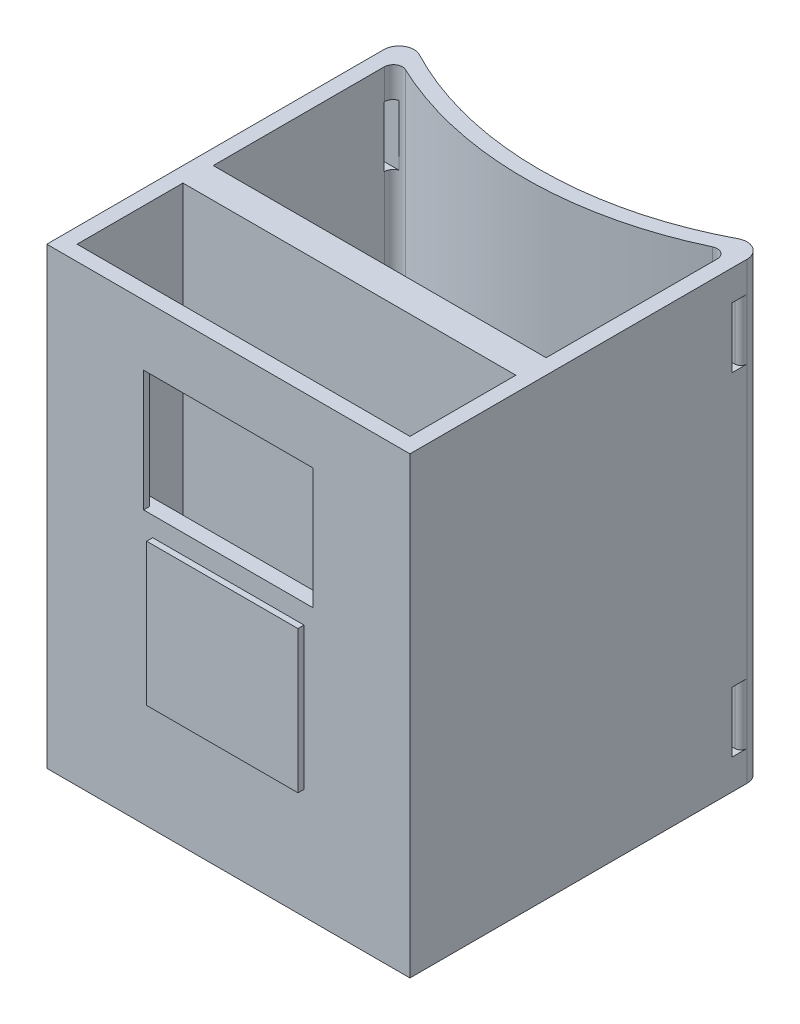
SolidWorks part; units mm, degrees
ref_plane "Front Plane" through (0, 0, 0) normal (0, 0, 1) x (1, 0, 0)
ref_plane "Top Plane" through (0, 0, 0) normal (0, 1, 0) x (1, 0, 0)
ref_plane "Right Plane" through (0, 0, 0) normal (1, 0, 0) x (0, 0, -1)
sketch "Sketch1" plane through (0, 0, 0) normal (0, 1, 0) x (1, 0, 0)
  line L1 (-60, -60) -> (60, -60)
  line L2 (-60, -60) -> (-60, 60)
  line L3 (-60, 60) -> (60, 60)
  line L4 (60, -60) -> (60, 60)
  line L5 (-60, -60) -> (60, 60) construction
  line L6 (-60, 60) -> (60, -60) construction
  point P0 (0, 0)
  dimension "D1" = 120
  dimension "D2" = 120
extrude "Boss-Extrude1" add sketch "Sketch1" along normal blind 150
sketch "Sketch2" plane through (0, 150, 0) normal (0, 1, 0) x (1, 0, 0)
  arc A0 (-60, 60) -> (60, 60) centre (0, 155.9682) ccw
extrude "Cut-Extrude1" cut sketch "Sketch2" against normal blind 150 and the other way through all
shell "Shell1" thickness 5 removed face at (0, 150, 4.3032)
sketch "Sketch3" plane through (0, 0, 0) normal (0, -1, 0) x (1, 0, 0)
  line L0 (60, 60) -> (60, -60) construction
  line L4 (-60, 60) -> (60, 60) construction
  circle A0 centre (0, 35) radius 2.5
  circle A1 centre (-5, 25) radius 1.5
  circle A2 centre (5, 25) radius 1.5
  point P9 (0, 0)
  dimension "D3" = 5
  dimension "D4" = 3
  dimension "D5" = 10
  dimension "D6" = 55
  dimension "D7" = 10
  dimension "D8" = 35
  dimension "D1" = 35
  dimension "D2" = 60
extrude "Cut-Extrude2" cut sketch "Sketch3" against normal up to next
fillet "Fillet1" radius 5 2 edges at (-60, 75, -60) (60, 75, -60)
sketch "Sketch4" plane through (0, 5, 0) normal (0, 1, 0) x (1, 0, 0)
  line L0 (-55, 51.3656) -> (-55, -55) construction
  line L1 (-55, -20) -> (55, -20)
  line L2 (-55, -20) -> (-55, -10)
  line L3 (-55, -10) -> (55, -10)
  line L4 (55, -20) -> (55, -10)
  line L5 (55, -55) -> (55, 51.3656) construction
  line L10 (-60, -60) -> (60, -60) construction
  point P12 (-33.8066, -60)
  dimension "D1" = 10
  dimension "D2" = 40
extrude "Boss-Extrude2" add sketch "Sketch4" along normal through all
sketch "Sketch5" plane through (0, 0, 60) normal (0, 0, 1) x (1, 0, 0)
  line L0 (60, 150) -> (60, 0) construction
  line L1 (-25, 36.5) -> (25, 36.5)
  line L2 (-25, 36.5) -> (-25, 83.5)
  line L3 (-25, 83.5) -> (25, 83.5)
  line L4 (25, 36.5) -> (25, 83.5)
  line L5 (-25, 36.5) -> (25, 83.5) construction
  line L6 (-25, 83.5) -> (25, 36.5) construction
  line L7 (-60, 150) -> (60, 150) construction
  point P0 (0, 60)
  dimension "D1" = 50
  dimension "D2" = 47
  dimension "D3" = 60
  dimension "D4" = 90
extrude "Boss-Extrude3" add sketch "Sketch5" along normal blind 2
sketch "Sketch8" plane through (0, 0, 60) normal (0, 0, 1) x (1, 0, 0)
  line L0 (-60, 150) -> (-60, 0) construction
  line L1 (-28, 89.9432) -> (28, 89.9432)
  line L2 (-28, 89.9432) -> (-28, 129.9432)
  line L3 (-28, 129.9432) -> (28, 129.9432)
  line L4 (28, 89.9432) -> (28, 129.9432)
  line L5 (-28, 89.9432) -> (28, 129.9432) construction
  line L6 (-28, 129.9432) -> (28, 89.9432) construction
  point P0 (0, 109.9432)
  dimension "D1" = 56
  dimension "D2" = 40
  dimension "D3" = 60
extrude "Cut-Extrude3" cut sketch "Sketch8" against normal up to next
sketch "Sketch9" plane through (0, 0, 55) normal (0, 0, -1) x (-1, 0, 0)
  line L17 (28, 89.9432) -> (-28, 89.9432) construction
  line L18 (-28, 129.9432) -> (-35.5, 129.9432)
  line L19 (-28, 129.9432) -> (-28, 89.9432)
  line L20 (-28, 89.9432) -> (-35.5, 89.9432)
  line L21 (-35.5, 129.9432) -> (-35.5, 89.9432)
  line L22 (-28, 89.9432) -> (-28, 129.9432) construction
  line L23 (0, 89.9432) -> (0, 129.9432) construction
  line L24 (-28, 129.9432) -> (28, 129.9432) construction
  line L25 (28, 89.9432) -> (35.5, 89.9432)
  line L26 (35.5, 129.9432) -> (35.5, 89.9432)
  line L27 (28, 129.9432) -> (35.5, 129.9432)
  line L28 (28, 129.9432) -> (28, 89.9432)
  dimension "D1" = 40
  dimension "D2" = 0
  dimension "D3" = 7.5
  dimension "D4" = 0
extrude "Cut-Extrude4" cut sketch "Sketch9" against normal offset from surface (3 mm away) 2 up to face at (0, 109.9432, 60)
sketch "Sketch10" plane through (0, 0, 62) normal (0, 0, 1) x (1, 0, 0)
  line L0 (-25, 36.5) -> (25, 36.5) construction
  line L1 (-22.5, 81) -> (22.5, 81)
  line L2 (-22.5, 81) -> (-22.5, 39)
  line L3 (-22.5, 39) -> (22.5, 39)
  line L4 (22.5, 81) -> (22.5, 39)
  line L5 (25, 36.5) -> (25, 83.5) construction
  point P6 (0, 0)
  dimension "D1" = 45
  dimension "D2" = 42
  dimension "D3" = 2.5
  dimension "D4" = 2.5
extrude "Cut-Extrude5" cut sketch "Sketch10" against normal up to next from offset 4 offset against normal yes
sketch "Sketch11" plane through (60, 0, 0) normal (1, 0, 0) x (0, 0, -1)
  line L1 (49.3656, 10) -> (46.3656, 10)
  line L2 (49.3656, 10) -> (49.3656, 30)
  line L3 (49.3656, 30) -> (46.3656, 30)
  line L4 (46.3656, 10) -> (46.3656, 30)
  line L5 (51.3656, 0) -> (51.3656, 150) construction
  line L6 (-60, 0) -> (51.3656, 0) construction
  line L7 (-60, 75) -> (51.3656, 75) construction
  line L8 (-60, 150) -> (-60, 0) construction
  line L9 (49.3656, 120) -> (46.3656, 120)
  line L10 (46.3656, 140) -> (46.3656, 120)
  line L11 (49.3656, 140) -> (46.3656, 140)
  line L12 (49.3656, 140) -> (49.3656, 120)
  dimension "D1" = 3
  dimension "D2" = 20
  dimension "D3" = 5
  dimension "D4" = 10
extrude "Cut-Extrude6" cut sketch "Sketch11" against normal up to next
ref_plane "Plane1" through (0, 0, 0) normal (-1, 0, 0) x (0, 0, 1)
mirror "Mirror1" about plane through (0, 0, 0) normal (-1, 0, 0) of "Cut-Extrude6"
fillet "Fillet3" radius 2 4 edges at (-60, 20, -49.3656) (-60, 130, -49.3656) (60, 20, -49.3656) (60, 130, -49.3656)
fillet "Fillet5" radius 3 2 edges at (-55, 77.5, -51.3656) (55, 77.5, -51.3656)
